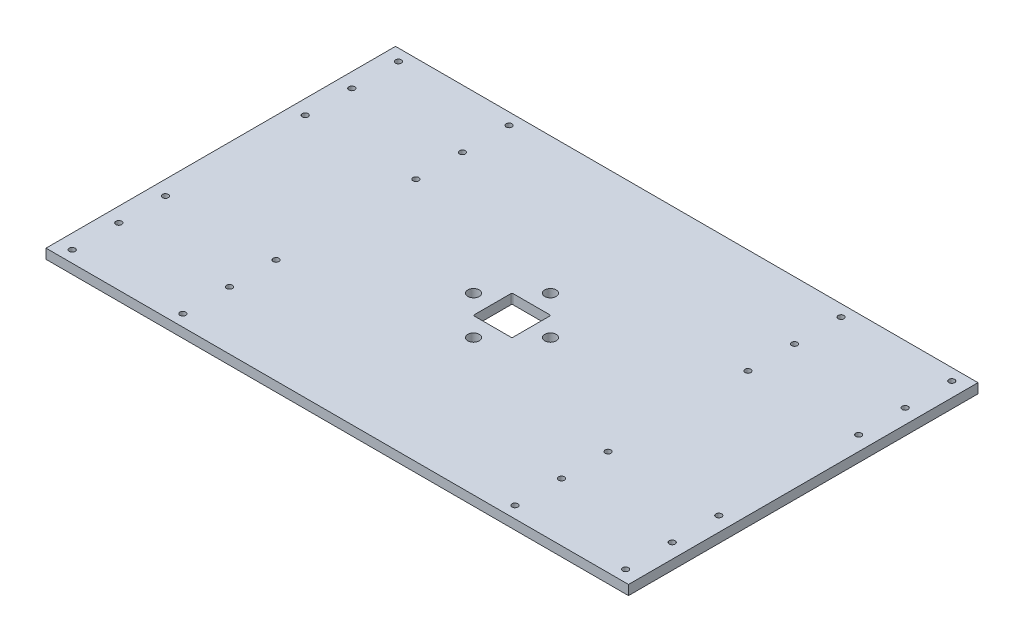
SolidWorks part; units mm, degrees
ref_plane "Front Plane" through (0, 0, 0) normal (0, 0, 1) x (1, 0, 0)
ref_plane "Top Plane" through (0, 0, 0) normal (0, 1, 0) x (1, 0, 0)
ref_plane "Right Plane" through (0, 0, 0) normal (1, 0, 0) x (0, 0, -1)
sketch "Sketch1" plane through (0, 0, 0) normal (0, 1, 0) x (1, 0, 0)
  line L0 (-142.5, 90) -> (-142.5, -90) construction
  line L1 (-150, -90) -> (150, -90)
  line L2 (-150, -90) -> (-150, 90)
  line L3 (-150, 90) -> (150, 90)
  line L4 (150, -90) -> (150, 90)
  line L5 (-150, -90) -> (150, 90) construction
  line L6 (-150, 90) -> (150, -90) construction
  line L8 (0, 90) -> (0, -90) construction
  line L9 (-150, 0) -> (150, 0) construction
  line L10 (-9.5, -10) -> (9.5, -10)
  line L11 (-10, -9.5) -> (-10, 9.5)
  line L12 (-9.5, 10) -> (9.5, 10)
  line L13 (10, -9.5) -> (10, 9.5)
  line L14 (-10, -10) -> (10, 10) construction
  line L15 (-10, 10) -> (10, -10) construction
  circle A0 centre (-142.5, 84) radius 1.5
  circle A1 centre (-142.5, 60) radius 1.5
  circle A2 centre (-142.5, 36) radius 1.5
  circle A3 centre (-85.5, 84) radius 1.5
  circle A4 centre (-85.5, 60) radius 1.5
  circle A5 centre (-85.5, 36) radius 1.5
  circle A6 centre (85.5, 36) radius 1.5
  circle A7 centre (85.5, 60) radius 1.5
  circle A8 centre (85.5, 84) radius 1.5
  circle A9 centre (142.5, 36) radius 1.5
  circle A10 centre (142.5, 60) radius 1.5
  circle A11 centre (142.5, 84) radius 1.5
  circle A12 centre (142.5, -84) radius 1.5
  circle A13 centre (142.5, -60) radius 1.5
  circle A14 centre (142.5, -36) radius 1.5
  circle A15 centre (85.5, -84) radius 1.5
  circle A16 centre (85.5, -60) radius 1.5
  circle A17 centre (85.5, -36) radius 1.5
  circle A18 centre (-85.5, -36) radius 1.5
  circle A19 centre (-85.5, -60) radius 1.5
  circle A20 centre (-85.5, -84) radius 1.5
  circle A21 centre (-142.5, -36) radius 1.5
  circle A22 centre (-142.5, -60) radius 1.5
  circle A23 centre (-142.5, -84) radius 1.5
  arc A24 (9.5, 10) -> (10, 9.5) centre (9.5, 9.5) cw
  arc A25 (10, -9.5) -> (9.5, -10) centre (9.5, -9.5) cw
  arc A26 (-9.5, -10) -> (-10, -9.5) centre (-9.5, -9.5) cw
  arc A27 (-10, 9.5) -> (-9.5, 10) centre (-9.5, 9.5) cw
  circle A28 centre (0, 19.8) radius 2.95
  circle A29 centre (19.8, 0) radius 2.95
  circle A30 centre (0, -19.8) radius 2.95
  circle A31 centre (-19.8, 0) radius 2.95
  point P0 (0, 0)
  point P59 (0, 0)
  point P88 (0, 0)
  dimension "D5" = 3
  dimension "D9" = 0.5
  dimension "D10" = 9.8
  dimension "D11" = 5.9
  dimension "D14" = 57
  dimension "D1" = 300
  dimension "D2" = 180
  dimension "D3" = 7.5
  dimension "D4" = 3
  dimension "D6" = 6
  dimension "D8" = 20
  dimension "D13" = 24
  dimension "D7" = 2
  dimension "D12" = 4
extrude "Boss-Extrude1" add sketch "Sketch1" along normal blind 5
